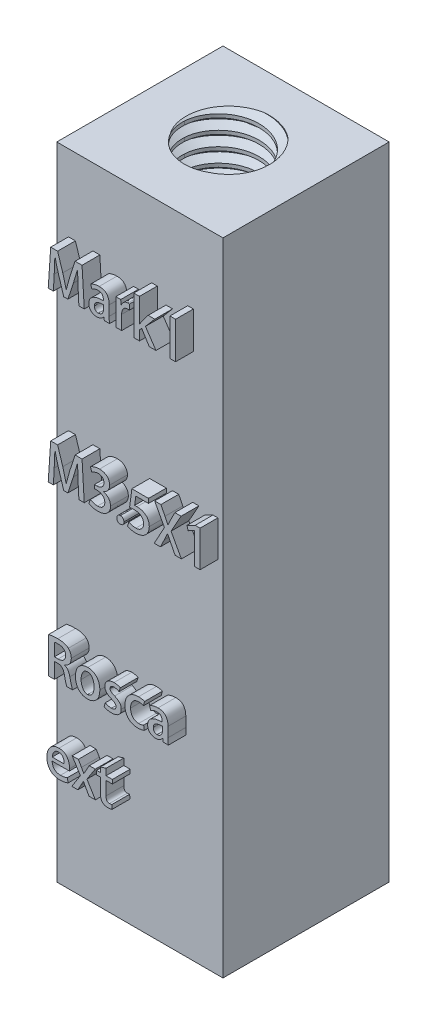
SolidWorks part; units mm, degrees
ref_plane "Alzado" through (0, 0, 0) normal (0, 0, 1) x (1, 0, 0)
ref_plane "Planta" through (0, 0, 0) normal (0, 1, 0) x (1, 0, 0)
ref_plane "Vista lateral" through (0, 0, 0) normal (1, 0, 0) x (0, 0, -1)
sketch "Croquis1" plane through (0, 0, 0) normal (0, 1, 0) x (1, 0, 0)
  line L1 (-3.5, 3.5) -> (3.5, 3.5)
  line L2 (-3.5, 3.5) -> (-3.5, -3.5)
  line L3 (-3.5, -3.5) -> (3.5, -3.5)
  line L4 (3.5, 3.5) -> (3.5, -3.5)
  line L5 (-3.5, 3.5) -> (3.5, -3.5) construction
  line L6 (-3.5, -3.5) -> (3.5, 3.5) construction
  circle A0 centre (0, 0) radius 1.625
  point P0 (0, 0)
  dimension "D1" = 3.25
  dimension "7" = 7
extrude "Saliente-Extruir1" add sketch "Croquis1" along normal blind 27
sketch "Croquis2" plane through (0, 0, 3.5) normal (0, 0, 1) x (1, 0, 0)
  text T0 "Mark I\r\n \r\nM3.5X1\r\n\r\nRosca\r\next" font "@Adobe Heiti Std R" height in points 5
split line "Línea de partición1"
extrude "Saliente-Extruir2" add sketch "Croquis2<2>" along normal blind 0.75
sketch "Croquis2<2>" plane through (0, 0, 3.5) normal (0, 0, 1) x (1, 0, 0) same geometry as "Croquis2"
thread "Rosca1" pitch 0.6 method cut profile "Perfil de rosca1" start angle 0, offset 1, length 18, pitch 0.6, diameter 3.25
ref_plane "Plano1" through (-1.625, 28, 0) normal (0, 0, 1) x (-1, 0, 0)
sketch "Perfil de rosca1" plane through (-1.625, 28, 0) normal (0, 0, 1) x (-1, 0, 0)
  line L0 (0, 0) -> (0, 0.6) construction
  line L1 (0, 0) -> (0.3248, 0.1875)
  line L2 (0.3248, 0.1875) -> (0.3248, 0.2625)
  line L3 (0.3248, 0.2625) -> (0, 0.45)
  line L4 (0.3248, 0.225) -> (0, 0.225) construction
  line L11 (0, 0) -> (0, 0.45)
  point P2 (0, 0)
  dimension "Pitch" = 0.6
  dimension "Profile_Angle" = 60
  dimension "Profile_Land" = 0.075
  dimension "Profile_Height" = 0.3248
